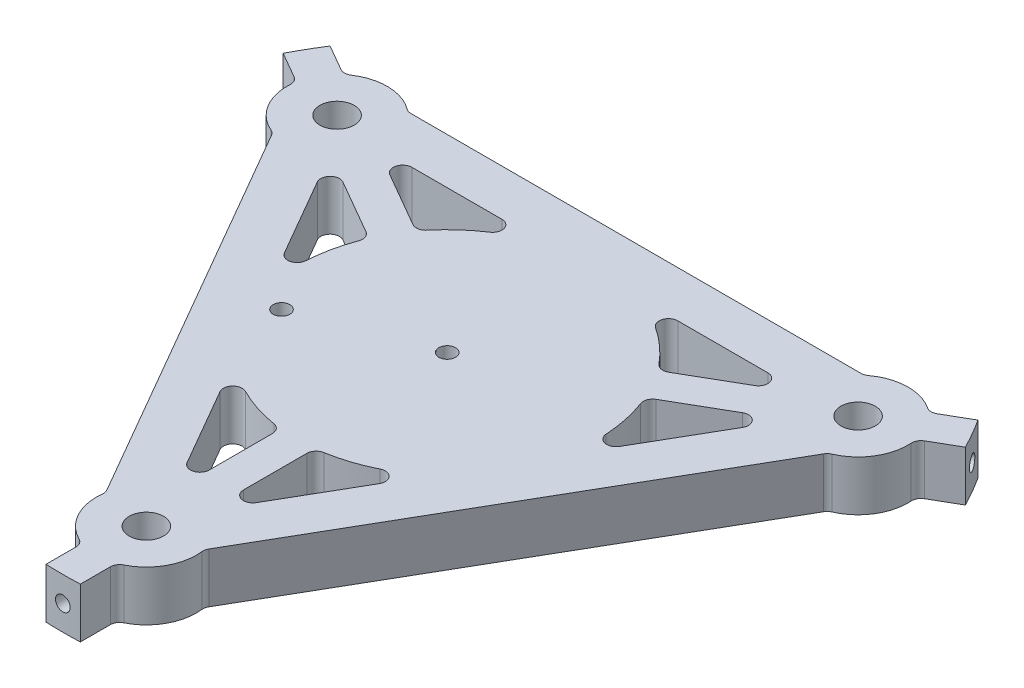
SolidWorks part; units mm, degrees
material "ABS"
ref_plane "Front Plane" through (0, 0, 0) normal (0, 0, 1) x (1, 0, 0)
ref_plane "Top Plane" through (0, 0, 0) normal (0, 1, 0) x (1, 0, 0)
ref_plane "Right Plane" through (0, 0, 0) normal (1, 0, 0) x (0, 0, -1)
sketch "Sketch1" plane through (0, 0, 0) normal (0, 1, 0) x (1, 0, 0)
  line L0 (-3.2639, -67.2662) -> (-3.2639, -72.952)
  line L1 (3.2639, -67.2662) -> (3.2639, -72.952)
  line L2 (3.2639, -41.9471) -> (3.2639, -29.9313)
  line L3 (-3.2639, -41.9471) -> (-3.2639, -29.9313)
  line L4 (-34.6953, 23.8002) -> (-24.2893, 17.7923)
  line L5 (-37.9592, 18.1469) -> (-27.5532, 12.139)
  line L6 (-56.6223, 36.4597) -> (-61.5464, 39.3026)
  line L7 (-59.8862, 30.8065) -> (-64.8103, 33.6494)
  line L8 (37.9592, 18.1469) -> (27.5532, 12.139)
  line L9 (34.6953, 23.8002) -> (24.2893, 17.7923)
  line L10 (59.8862, 30.8065) -> (64.8103, 33.6494)
  line L11 (56.6223, 36.4597) -> (61.5464, 39.3026)
  line L12 (0, 0) -> (0, -57.15) construction
  line L13 (0, 0) -> (-49.4934, 28.575) construction
  line L14 (0, 0) -> (49.4934, 28.575) construction
  line L15 (40.388, 15.7181) -> (31.8393, 0.9115)
  line L16 (9.6892, -54.9694) -> (52.4495, 19.0936)
  line L17 (-6.5817, -42.8361) -> (-15.1303, -28.0294)
  line L18 (-52.4495, 19.0936) -> (-9.6892, -54.9694)
  line L19 (-42.7603, 35.8758) -> (42.7603, 35.8758)
  line L20 (-33.8063, 27.118) -> (-16.709, 27.118)
  line L21 (16.709, 27.118) -> (33.8063, 27.118)
  line L22 (-31.8393, 0.9115) -> (-40.388, 15.7181)
  line L23 (15.1303, -28.0294) -> (6.5817, -42.8361)
  arc A0 (-3.2639, -72.952) -> (3.2639, -72.952) centre (0, 0) ccw
  arc A1 (4.7466, -28.178) -> (12.7944, -25.5506) centre (0, 0) ccw
  arc A2 (-9.4626, -56.0616) -> (-4.2488, -65.6749) centre (0, -57.15) ccw
  circle A3 centre (0, -57.15) radius 3.2639
  arc A4 (4.2488, -65.6749) -> (9.4626, -56.0616) centre (0, -57.15) ccw
  arc A5 (-43.8195, 36.2257) -> (-54.7517, 36.517) centre (-49.4934, 28.575) ccw
  arc A6 (-61.5464, 39.3026) -> (-64.8103, 33.6494) centre (0, 0) ccw
  arc A7 (-59.0005, 29.1579) -> (-53.2821, 19.8359) centre (-49.4934, 28.575) ccw
  circle A8 centre (-49.4934, 28.575) radius 3.2639
  arc A9 (53.2821, 19.8359) -> (59.0005, 29.1579) centre (49.4934, 28.575) ccw
  arc A10 (64.8103, 33.6494) -> (61.5464, 39.3026) centre (0, 0) ccw
  arc A11 (54.7517, 36.517) -> (43.8195, 36.2257) centre (49.4934, 28.575) ccw
  circle A12 centre (49.4934, 28.575) radius 3.2639
  arc A13 (-26.7762, 9.9784) -> (-28.5247, 1.695) centre (0, 0) ccw
  arc A14 (22.0296, 18.1997) -> (15.7302, 23.8556) centre (0, 0) ccw
  circle A15 centre (0, 0) radius 1.5875
  arc A16 (-12.7944, -25.5506) -> (-4.7466, -28.178) centre (0, 0) ccw
  arc A17 (28.5247, 1.695) -> (26.7762, 9.9784) centre (0, 0) ccw
  arc A18 (-15.7302, 23.8556) -> (-22.0296, 18.1997) centre (0, 0) ccw
  arc A19 (37.9592, 18.1469) -> (40.388, 15.7181) centre (38.8482, 16.6071) cw
  arc A20 (26.7762, 9.9784) -> (27.5532, 12.139) centre (28.4422, 10.5992) cw
  arc A21 (3.2639, -29.9313) -> (4.7466, -28.178) centre (5.0419, -29.9313) cw
  arc A22 (15.1303, -28.0294) -> (12.7944, -25.5506) centre (13.5905, -27.1404) ccw
  arc A23 (6.5817, -42.8361) -> (3.2639, -41.9471) centre (5.0419, -41.9471) cw
  arc A24 (-6.5817, -42.8361) -> (-3.2639, -41.9471) centre (-5.0419, -41.9471) ccw
  arc A25 (-3.2639, -29.9313) -> (-4.7466, -28.178) centre (-5.0419, -29.9313) ccw
  arc A26 (-15.1303, -28.0294) -> (-12.7944, -25.5506) centre (-13.5905, -27.1404) cw
  arc A27 (-31.8393, 0.9115) -> (-28.5247, 1.695) centre (-30.2996, 1.8005) ccw
  arc A28 (-26.7762, 9.9784) -> (-27.5532, 12.139) centre (-28.4422, 10.5992) ccw
  arc A29 (-40.388, 15.7181) -> (-37.9592, 18.1469) centre (-38.8482, 16.6071) cw
  arc A30 (-24.2893, 17.7923) -> (-22.0296, 18.1997) centre (-23.4003, 19.3321) ccw
  arc A31 (-34.6953, 23.8002) -> (-33.8063, 27.118) centre (-33.8063, 25.34) cw
  arc A32 (-15.7302, 23.8556) -> (-16.709, 27.118) centre (-16.709, 25.34) ccw
  arc A33 (-4.2488, -65.6749) -> (-3.2639, -67.2662) centre (-5.0419, -67.2662) cw
  arc A34 (3.2639, -67.2662) -> (4.2488, -65.6749) centre (5.0419, -67.2662) cw
  arc A35 (9.6892, -54.9694) -> (9.4626, -56.0616) centre (11.229, -55.8584) ccw
  arc A36 (-9.4626, -56.0616) -> (-9.6892, -54.9694) centre (-11.229, -55.8584) ccw
  arc A37 (-52.4495, 19.0936) -> (-53.2821, 19.8359) centre (-53.9893, 18.2046) ccw
  arc A38 (-59.0005, 29.1579) -> (-59.8862, 30.8065) centre (-60.7752, 29.2667) ccw
  arc A39 (-56.6223, 36.4597) -> (-54.7517, 36.517) centre (-55.7333, 37.9995) ccw
  arc A40 (-43.8195, 36.2257) -> (-42.7603, 35.8758) centre (-42.7603, 37.6538) ccw
  arc A41 (42.7603, 35.8758) -> (43.8195, 36.2257) centre (42.7603, 37.6538) ccw
  arc A42 (52.4495, 19.0936) -> (53.2821, 19.8359) centre (53.9893, 18.2046) cw
  arc A43 (54.7517, 36.517) -> (56.6223, 36.4597) centre (55.7333, 37.9995) ccw
  arc A44 (59.0005, 29.1579) -> (59.8862, 30.8065) centre (60.7752, 29.2667) cw
  arc A45 (15.7302, 23.8556) -> (16.709, 27.118) centre (16.709, 25.34) cw
  arc A46 (34.6953, 23.8002) -> (33.8063, 27.118) centre (33.8063, 25.34) ccw
  arc A47 (22.0296, 18.1997) -> (24.2893, 17.7923) centre (23.4003, 19.3321) ccw
  arc A48 (31.8393, 0.9115) -> (28.5247, 1.695) centre (30.2996, 1.8005) cw
  point P53 (18.9808, -21.3603)
  point P64 (-27.9889, -5.7577)
  point P77 (-3.2639, -66.0983)
  point P80 (3.2639, -66.0983)
  point P103 (9.0082, 27.118)
  dimension "D1" = 146.05
  dimension "D2" = 57.15
  dimension "D3" = 19.05
  dimension "D4" = 6.5278
  dimension "D9" = 3.175
  dimension "D10" = 1.778
  dimension "D11" = 1.778
  dimension "D5" = 57.15
  dimension "D7" = 120
  dimension "D8" = 120
  dimension "D6" = 3
extrude "Boss-Extrude1" add sketch "Sketch1" along normal mid plane 9.525
sketch "Sketch2" plane through (0, 0, 0) normal (0, 0, 1) x (1, 0, 0)
  line L0 (0, 4.7625) -> (0, -4.7625) construction
  line L1 (3.2639, 4.7625) -> (-3.2639, 4.7625) construction
  line L2 (-3.2639, -4.7625) -> (3.2639, -4.7625) construction
ref_plane "Plane1" through (0, 0, 73.025) normal (0, 0, 1) x (1, 0, 0)
sketch "Sketch3" plane through (0, 0, 73.025) normal (0, 0, 1) x (1, 0, 0)
  circle A0 centre (0, 0) radius 1.397
  dimension "D1" = 2.794
extrude "Cut-Extrude1" cut sketch "Sketch3" against normal blind 6.35
pattern_circular "CirPattern1" count 3 over 360 about axis through (0, 4.7625, 0) along (0, -1, 0) of "Cut-Extrude1"
sketch "Sketch4" plane through (0, -4.7625, 0) normal (0, -1, 0) x (1, 0, 0)
  circle A0 centre (-22.821, 8.6514) radius 1.5875
  dimension "D1" = 3.175
extrude "Cut-Extrude2" cut sketch "Sketch4" against normal through all both and the other way through all
equation "\"Bodytube_OD\" = 6.17in"
equation "\"Bodytube_ID\" = 5.998in"
equation "\"Motor_OD\" = 4in"
equation "\"Fwd_Tube_Length\" = 38in"
equation "\"Mid_Tube_Length\" = 8in"
equation "\"Aft_Section_Length\"= 40in"
equation "\"Mid_Coupler_Length\" = 13in"
equation "\"Aft_Lower_Length\"= 22in"
equation "\"AB_Coupler_OD_Length\"= 1in"
equation "\"AB_Coupling_Section_Length\"= 0.375in"
equation "\"AB_Coupler_Length\"= \"AB_Coupler_OD_Length\" + \"AB_Coupling_Section_Length\" * 2"
equation "\"Cutout_Angle\" = 80"
equation "\"AB_Paddle_Height\" = 0.375in"
equation "\"AB_Coupler_Num_Screws\"= 6"
equation "\"Num_Cutouts\" = 3"
equation "\"AB_Coupler_OD\"= 6.17in"
equation "\"AB_Coupler_ID\"= 5.75in"
equation "\"AB_Coupler_Surface_Diameter\"= 5.998in"
equation "\"AB_Coupling_Screw_Diameter\"= 0.1065in"
equation "\"AB_Central_Bushing_Length\" = .75in"
equation "\"Lead_Screw_Dist\" = 2.25in"
equation "\"Lead_Screw_Diam\" = (27/64)*1in"
equation "\"Lead_Screw_Length\" = (\"Mid_Coupler_Length\" + 2*0.375in + 2*0.5in)"
equation "\"Paddle_Pin_Offset\" = .25in"
equation "\"Paddle_Pin_Radius\" = 2.25in"
equation "\"Paddle_Gear_OD\" = 3.2in"
equation "\"Fwd_BKHD_From_Top\" = 18in"
equation "\"Fin_Thickness\"= .118in"
equation "\"Guiderail_Cutout_Diameter\"= 1.5in"
equation "\"D5@Sketch1\"=\"Paddle_Pin_Radius\""
